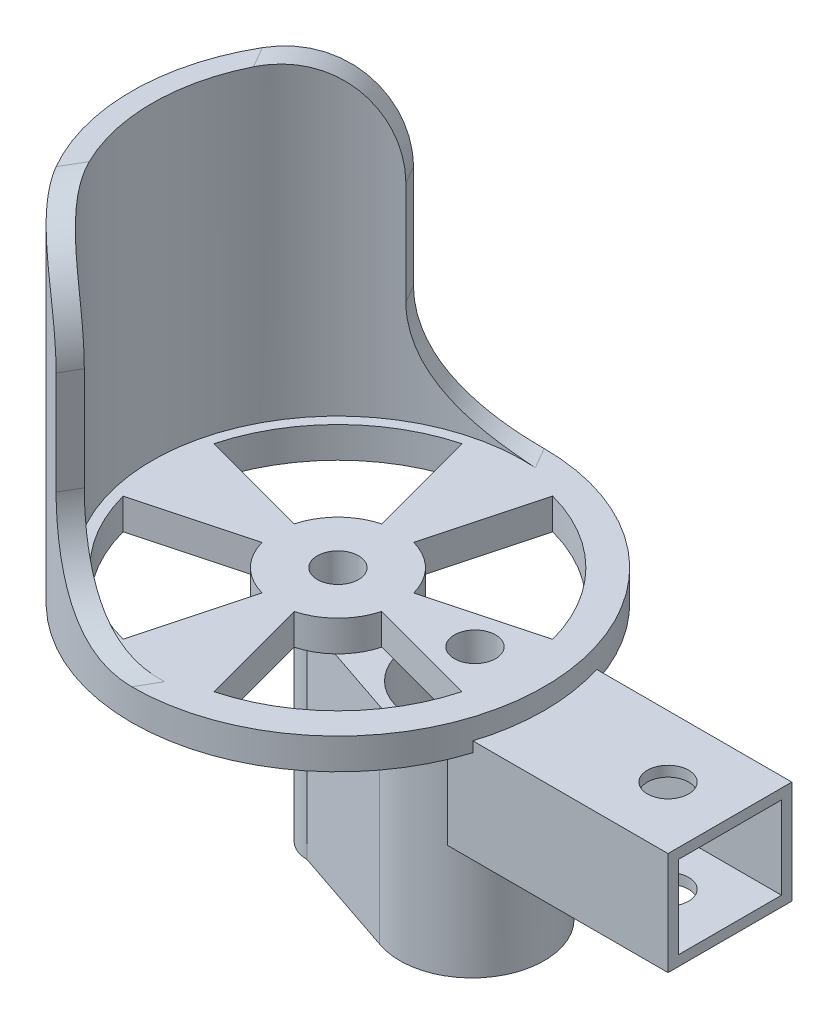
SolidWorks part; units mm, degrees
material "ABS"
ref_plane "前视基准面" through (0, 0, 0) normal (0, 0, 1) x (1, 0, 0)
ref_plane "上视基准面" through (0, 0, 0) normal (0, 1, 0) x (1, 0, 0)
ref_plane "右视基准面" through (0, 0, 0) normal (1, 0, 0) x (0, 0, -1)
sketch "草图1" plane through (0, 0, 0) normal (0, 1, 0) x (1, 0, 0)
  line L0 (0, 0) -> (3, 0)
  line L1 (0, 0) -> (0, 3)
  line L2 (0.7765, 2.8978) -> (2.2, 8.2104)
  line L3 (2.8978, 0.7765) -> (8.2104, 2.2)
  line L4 (2.8978, -0.7765) -> (8.2104, -2.2)
  line L5 (0.7765, -2.8978) -> (2.2, -8.2104)
  line L6 (-0.7765, -2.8978) -> (-2.2, -8.2104)
  line L7 (-2.8978, -0.7765) -> (-8.2104, -2.2)
  line L8 (-2.8978, 0.7765) -> (-8.2104, 2.2)
  line L9 (-0.7765, 2.8978) -> (-2.2, 8.2104)
  circle A0 centre (0, 0) radius 10
  arc A1 (8.2104, 2.2) -> (2.2, 8.2104) centre (0, 0) ccw
  arc A3 (2.8978, 0.7765) -> (0.7765, 2.8978) centre (0, 0) ccw
  arc A4 (2.2, -8.2104) -> (8.2104, -2.2) centre (0, 0) ccw
  arc A5 (0.7765, -2.8978) -> (2.8978, -0.7765) centre (0, 0) ccw
  arc A6 (-8.2104, -2.2) -> (-2.2, -8.2104) centre (0, 0) ccw
  arc A7 (-2.8978, -0.7765) -> (-0.7765, -2.8978) centre (0, 0) ccw
  arc A8 (-2.2, 8.2104) -> (-8.2104, 2.2) centre (0, 0) ccw
  arc A9 (-0.7765, 2.8978) -> (-2.8978, 0.7765) centre (0, 0) ccw
  point P24 (0, 0)
  dimension "D1" = 15
  dimension "D2" = 15
  dimension "D3" = 4
extrude "凸台-拉伸1" add sketch "草图1" along normal blind 1.5 contours A0 L3 A3 L2 A1 L5 A5 L4 A4 L7 A7 L6 A6 L9 A9 L8 A8 region at (-9.7172, 0, 0)
sketch "草图2" plane through (0, 1.5, 0) normal (0, 1, 0) x (1, 0, 0)
  line L2 (-4.5, 7.7942) -> (-5, 8.6603)
  line L3 (-4.5, -7.7942) -> (-5, -8.6603)
  arc A1 (-5, 8.6603) -> (-5, -8.6603) centre (0, 0) ccw
  arc A2 (-4.5, 7.7942) -> (-4.5, -7.7942) centre (0, 0) ccw
  dimension "D2" = 120
extrude "凸台-拉伸2" add sketch "草图2" along normal blind 15
fillet "圆角1" radius 5 4 edges at (-4.75, 1.5, 8.2272) (-4.75, 1.5, -8.2272) (-4.75, 16.5, 8.2272) (-4.75, 16.5, -8.2272)
sketch "草图3" plane through (0, 0, 0) normal (0, -1, 0) x (1, 0, 0)
  line L0 (0, 0) -> (6.5, 0)
  line L1 (0, 1.5) -> (5.4395, 3.3355)
  line L2 (0, -1.5) -> (5.3807, -3.3162)
  circle A0 centre (0, 0) radius 1
  circle A1 centre (0, 0) radius 1.5
  circle A2 centre (6.5, 0) radius 3.5
  circle A3 centre (6.5, 0) radius 3
  line M2 (2.8978, -0.7765) -> (8.2104, -2.2)
  arc M5 (0.7765, -2.8978) -> (2.8978, -0.7765) centre (0, 0) ccw
  line M8 (8.2104, 2.2) -> (2.8978, 0.7765)
  arc M9 (2.8978, 0.7765) -> (0.7765, 2.8978) centre (0, 0) ccw
extrude "凸台-拉伸3" add sketch "草图3" along normal blind 10 contours A2 L1 M9 M8 | A2 L1 A1 L0 M8 M9 | A2 L0 A1 L2 M5 M2 | A2 L2 M2 M5 | A1 A0 | A2 | A3 region at (1.0307, 0, -1.0307) region at (1.8981, 0, 1.0407) region at (1.8981, 0, -1.0408) region at (3.1928, 0, 2.0386) region at (3.1933, 0, -2.0391)
ref_plane "基准面4" through (7, 0, 0) normal (1, 0, 0) x (0, 0, -1)
sketch "草图4" plane through (7, 0, 0) normal (1, 0, 0) x (0, 0, -1)
  line L0 (0, 0) -> (0, -2)
  line L2 (2.5, -4) -> (-2.5, -4)
  line L3 (2.5, -4) -> (2.5, 0)
  line L4 (2.5, 0) -> (-2.5, 0)
  line L5 (-2.5, -4) -> (-2.5, 0)
  line L6 (2.5, -4) -> (-2.5, 0) construction
  line L7 (2.5, 0) -> (-2.5, -4) construction
  line L8 (3, -4.5) -> (-3, -4.5)
  line L9 (3, -4.5) -> (3, 0.5)
  line L10 (3, 0.5) -> (-3, 0.5)
  line L11 (-3, -4.5) -> (-3, 0.5)
  line L12 (3, -4.5) -> (-3, 0.5) construction
  line L13 (3, 0.5) -> (-3, -4.5) construction
extrude "凸台-拉伸4" add sketch "草图4" along normal blind 12 contours L10 L11 L8 L9 | L4 L5 L2 L3
sketch "草图5" plane through (0, -4.5, 0) normal (0, -1, 0) x (1, 0, 0)
  line L0 (19, 0) -> (17, 0)
  line L1 (19, -3) -> (19, 3) construction
  line L2 (17, 0) -> (16, 0)
  circle A1 centre (16, 0) radius 1
extrude "切除-拉伸1" cut sketch "草图5" against normal through all contours A1 region at (15.0283, -4.5, 0)
sketch "草图6" plane through (0, -10, 0) normal (0, -1, 0) x (1, 0, 0)
  circle A0 centre (6.5, 0) radius 3
extrude "切除-拉伸2" cut sketch "草图6" against normal blind 10
sketch "草图7" plane through (0, 0, 0) normal (0, -1, 0) x (1, 0, 0)
  circle A0 centre (6.6425, 0) radius 1
extrude "切除-拉伸3" cut sketch "草图7" against normal through all
sketch "草图8" plane through (0, 0, 0) normal (0, -1, 0) x (1, 0, 0)
  circle A0 centre (0, 0) radius 1
extrude "切除-拉伸4" cut sketch "草图8" against normal through all
